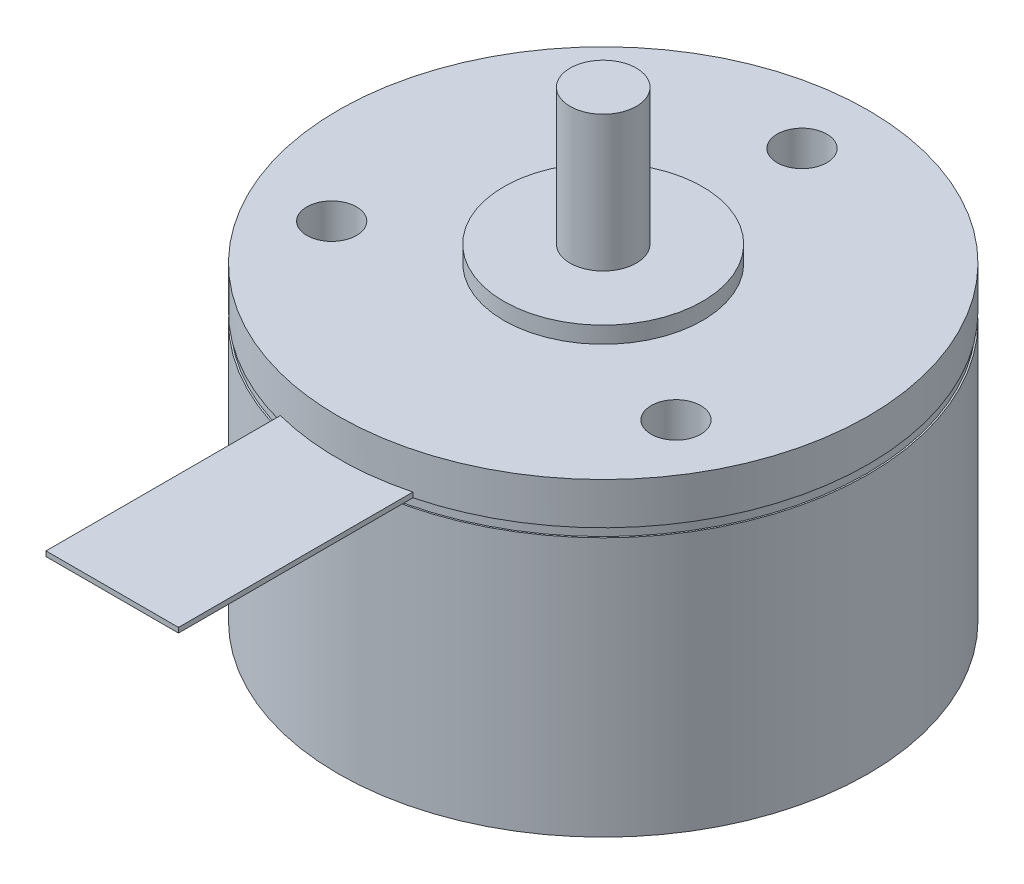
SolidWorks part; units mm, degrees
ref_plane "Alzado" through (0, 0, 0) normal (0, 0, 1) x (1, 0, 0)
ref_plane "Planta" through (0, 0, 0) normal (0, 1, 0) x (1, 0, 0)
ref_plane "Vista lateral" through (0, 0, 0) normal (1, 0, 0) x (0, 0, -1)
sketch "Croquis1" plane through (0, 0, 0) normal (0, 1, 0) x (1, 0, 0)
  circle A0 centre (0, 0) radius 16
  circle A1 centre (0, 0) radius 6
  circle A2 centre (0, 0) radius 2
  circle A3 centre (0, 12) radius 1.5
  circle A4 centre (0, 0) radius 12
  circle A5 centre (10.3923, -6) radius 1.5
  circle A6 centre (-10.3923, -6) radius 1.5
  point P15 (0, 0)
  dimension "D1" = 32
  dimension "D2" = 12
  dimension "D3" = 4
  dimension "D4" = 3
  dimension "D5" = 24
  dimension "D6" = 3
extrude "Saliente-Extruir1" add sketch "Croquis1" along normal blind 2.2 contours A0 A6 A4 A3 A5 | A6 A4 A5 A3 A1 region at (-15.5475, 0, 0) region at (0, 0, -10.1613)
extrude "Saliente-Extruir2" add sketch "Croquis1<3>" along normal blind 3.2 separate body contours A1 A2 region at (-5.8303, 0, 0)
sketch "Croquis1<3>" plane through (0, 0, 0) normal (0, 1, 0) x (1, 0, 0) same geometry as "Croquis1"
extrude "Saliente-Extruir3" add sketch "Croquis1<4>" along normal blind 11.4 contours A2 region at (0, 0, 0)
sketch "Croquis1<4>" plane through (0, 0, 0) normal (0, 1, 0) x (1, 0, 0) same geometry as "Croquis1"
sketch "Croquis4" plane through (0, 0, 0) normal (1, 0, 0) x (0, 0, -1)
  line L1 (15.9091, -0.8474) -> (15.9091, -0.3226)
  line L2 (15.9091, -0.3226) -> (16, -0.3226)
  line L3 (16, 0) -> (16, -0.3226)
  line L6 (15.9091, -0.8474) -> (16, -0.8474)
  line L7 (16, -0.8474) -> (16, -16.5)
  line L8 (16, -16.5) -> (1.1, -16.5)
  line L9 (1.1, -16.5) -> (1, -16.5)
  line L10 (1, -16.5) -> (0, -16.5)
  line L11 (0, 0) -> (0, -16.5) construction
  line L12 (-16, 0) -> (16, 0) construction
  line L13 (16, 2.2) -> (-16, 2.2) construction
  line L15 (0, 0) -> (16, 0)
  line L16 (0, 0) -> (0, -16.5)
  line L17 (16, 0) -> (16, 2.2) construction
  dimension "D2" = 18.7
  dimension "D3" = 0.1
  dimension "D4" = 1
revolve "Revolución1" add sketch "Croquis4" angle 360 about L11
ref_plane "Plano1" through (0, -0.3226, 0) normal (0, -1, 0) x (-1, 0, 0)
sketch "Croquis5" plane through (0, -0.3226, 0) normal (0, -1, 0) x (-1, 0, 0)
  line L0 (-4, -9.081) -> (-4, -29.6412)
  line L1 (-4, -29.6412) -> (4, -29.6412)
  line L2 (4, -29.6412) -> (4, -9.081)
  line L3 (4, -9.081) -> (-4, -9.081)
  dimension "D1" = 4
  dimension "D2" = 8
extrude "Saliente-Extruir4" add sketch "Croquis5" against normal blind 0.3
